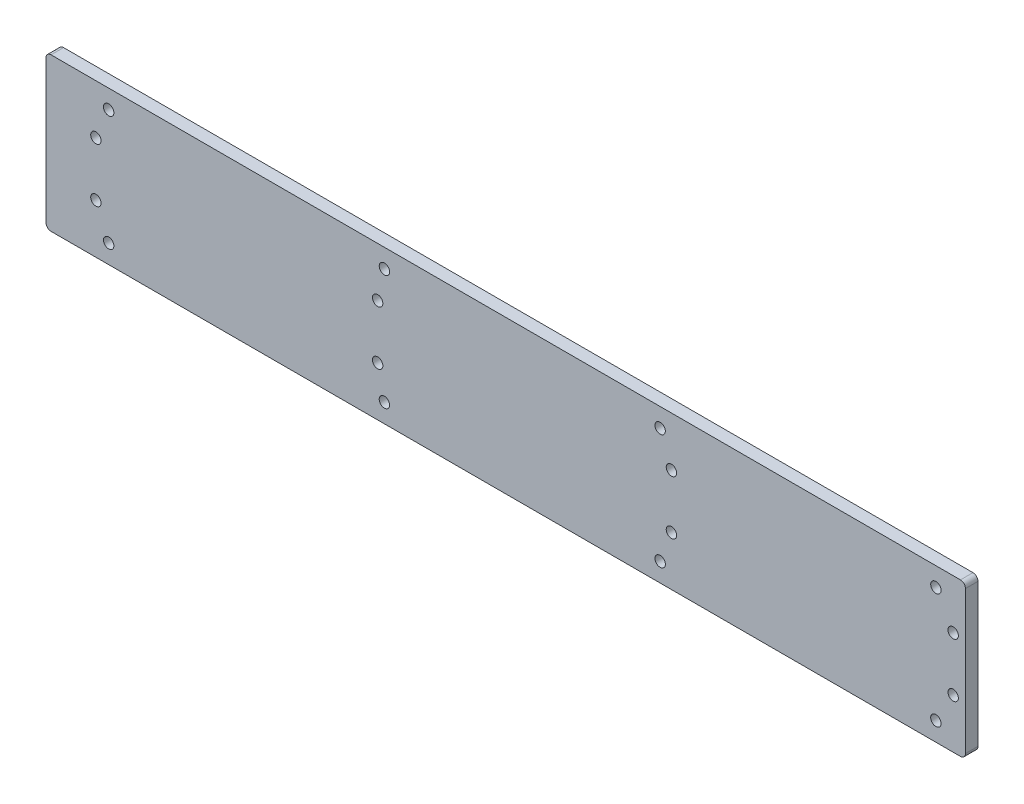
SolidWorks part; units mm, degrees
ref_plane "Alzado" through (0, 0, 0) normal (0, 0, 1) x (1, 0, 0)
ref_plane "Planta" through (0, 0, 0) normal (0, 1, 0) x (1, 0, 0)
ref_plane "Vista lateral" through (0, 0, 0) normal (1, 0, 0) x (0, 0, -1)
sketch "Croquis1" plane through (0, 0, 0) normal (0, 0, 1) x (1, 0, 0)
  line L1 (-8.795, -2.0974) -> (8.795, -2.0974)
  line L2 (-8.795, -2.0974) -> (-8.795, 2.0974)
  line L3 (-8.795, 2.0974) -> (8.795, 2.0974)
  line L4 (8.795, -2.0974) -> (8.795, 2.0974)
  line L5 (-8.795, -2.0974) -> (8.795, 2.0974) construction
  line L6 (-8.795, 2.0974) -> (8.795, -2.0974) construction
  point P0 (0, 0)
  dimension "D1" = 17.59
sketch "Croquis2" plane through (0, 0, 0) normal (0, 0, 1) x (1, 0, 0)
  line L0 (-242.443, -38.735) -> (-242.443, 38.735)
  line L1 (-223.393, -19.685) -> (223.393, -19.685) construction
  line L2 (-223.393, -19.685) -> (-223.393, 19.685) construction
  line L3 (-223.393, 19.685) -> (223.393, 19.685) construction
  line L4 (223.393, -19.685) -> (223.393, 19.685)
  line L5 (-223.393, -19.685) -> (223.393, 19.685) construction
  line L6 (-223.393, 19.685) -> (223.393, -19.685) construction
  line L7 (-242.443, 38.735) -> (223.393, 38.735)
  line L9 (-242.443, -38.735) -> (223.393, -38.735)
  line L10 (223.393, 19.685) -> (223.393, 38.735)
  line L11 (223.393, -19.685) -> (223.393, -38.735)
  line L12 (-242.443, 38.735) -> (242.443, 38.735) construction
  line L13 (242.443, -38.735) -> (242.443, 38.735) construction
  line L14 (-242.443, -38.735) -> (242.443, -38.735) construction
  point P0 (0, 0)
  dimension "D1" = 446.786
  dimension "D2" = 39.37
  dimension "D4" = 19.05
  dimension "D3" = 19.05
extrude "Saliente-Extruir1" add sketch "Croquis2" along normal blind 6.35
sketch "Croquis3" [suppressed] plane through (0, 0, 6.35) normal (0, 0, 1) x (1, 0, 0)
  line L0 (223.393, -38.735) -> (223.393, 38.735) construction
  line L1 (223.393, -19.685) -> (-223.393, -19.685)
  line L2 (223.393, -19.685) -> (223.393, 19.685)
  line L3 (223.393, 19.685) -> (-223.393, 19.685)
  line L4 (-223.393, -19.685) -> (-223.393, 19.685)
  line L5 (0, 0) -> (223.393, 0) construction
  line L6 (-242.443, 38.735) -> (-242.443, -38.735) construction
  line L7 (-242.443, -38.735) -> (223.393, -38.735) construction
  dimension "D1" = 19.05
  dimension "D2" = 446.786
  dimension "D3" = 19.05
  dimension "D4" = 39.37
extrude "Cortar-Extruir1" [suppressed] cut sketch "Croquis3" against normal through all
sketch "Croquis4" plane through (0, 0, 6.35) normal (0, 0, 1) x (1, 0, 0)
  line L0 (-9.525, 38.735) -> (-9.525, -38.735) construction
  line L1 (223.393, 38.735) -> (-242.443, 38.735) construction
  line L2 (-242.443, -38.735) -> (223.393, -38.735) construction
  line L3 (-217.17, 38.735) -> (-217.17, -38.735) construction
  line L4 (-242.443, 38.735) -> (-242.443, -38.735) construction
  line L5 (-242.443, 0) -> (223.393, 0) construction
  line L6 (223.393, -38.735) -> (223.393, 38.735) construction
  line L7 (-217.17, 16.3115) -> (-217.17, 11.049) construction
  line L8 (-217.17, -11.049) -> (-217.17, -16.3115) construction
  circle A0 centre (-217.17, 13.6802) radius 2.6312
  circle A1 centre (-217.17, -13.6802) radius 2.6312
  circle A2 centre (217.17, -13.6802) radius 2.6312
  circle A3 centre (217.17, 13.6802) radius 2.6312
  circle A4 centre (-74.422, 13.6802) radius 2.6313
  circle A5 centre (-74.422, -13.6802) radius 2.6313
  circle A6 centre (74.422, 13.6802) radius 2.6313
  circle A7 centre (74.422, -13.6802) radius 2.6313
  point P24 (-9.525, 0)
  dimension "D2" = 5.2625
  dimension "D1" = 25.273
  dimension "D3" = 22.098
  dimension "D4" = 142.748
  dimension "D5" = 142.748
  dimension "D6" = 148.844
  dimension "D7" = 6.223
  dimension "D8" = 27.3605
  dimension "D9" = 27.3605
extrude "Cortar-Extruir2" cut sketch "Croquis4" against normal through all
sketch "Croquis5" plane through (0, 0, 6.35) normal (0, 0, 1) x (1, 0, 0)
  line L0 (223.393, 19.685) -> (-223.393, 19.685) construction
  line L1 (223.393, -38.735) -> (223.393, 38.735) construction
  line L2 (-223.393, 19.685) -> (-223.393, -19.685) construction
  line L3 (-223.393, -19.685) -> (223.393, -19.685) construction
  line L4 (223.393, 38.735) -> (-242.443, 38.735) construction
  line L5 (-242.443, -38.735) -> (223.393, -38.735) construction
  line L6 (-242.443, 38.735) -> (-242.443, -38.735) construction
  line L7 (0, 38.735) -> (0, 19.685) construction
  line L8 (-223.393, 19.685) -> (-223.393, 38.735) construction
  line L9 (-223.393, 29.21) -> (223.393, 29.21) construction
  line L10 (-223.393, 0) -> (223.393, 0) construction
  circle A0 centre (-210.693, 29.21) radius 2.6312
  circle A1 centre (-70.993, 29.21) radius 2.6313
  circle A2 centre (68.707, 29.21) radius 2.6313
  circle A3 centre (208.407, 29.21) radius 2.6312
  circle A4 centre (208.407, -29.21) radius 2.6312
  circle A5 centre (68.707, -29.21) radius 2.6313
  circle A6 centre (-70.993, -29.21) radius 2.6313
  circle A7 centre (-210.693, -29.21) radius 2.6312
  dimension "D4" = 5.2625
  dimension "D1" = 19.05
  dimension "D2" = 19.05
  dimension "D3" = 19.05
  dimension "D5" = 12.7
  dimension "D7" = 139.7
  dimension "D6" = 4
extrude "Cortar-Extruir3" cut sketch "Croquis5" against normal through all
fillet "Redondeo1" radius 2.54 4 edges at (223.393, -38.735, 3.175) (223.393, 38.735, 3.175) (-242.443, -38.735, 3.175) (-242.443, 38.735, 3.175)
fillet "Redondeo2" [suppressed] radius 2.54
